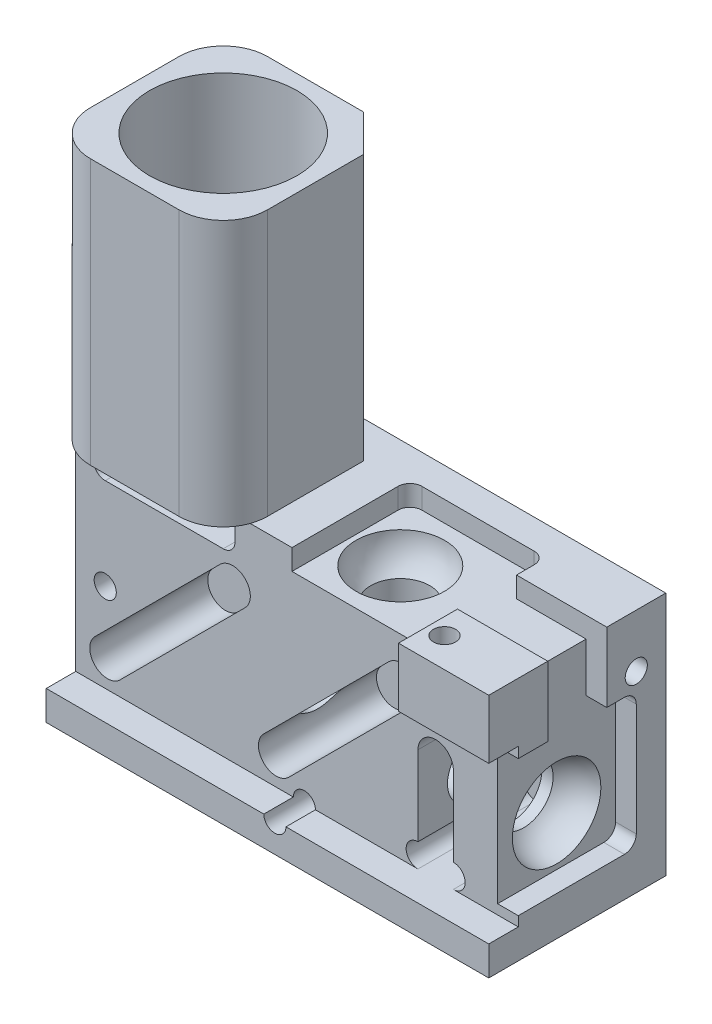
SolidWorks part; units mm, degrees
ref_plane "Front Plane" through (0, 0, 0) normal (0, 0, 1) x (1, 0, 0)
ref_plane "Top Plane" through (0, 0, 0) normal (0, 1, 0) x (1, 0, 0)
ref_plane "Right Plane" through (0, 0, 0) normal (1, 0, 0) x (0, 0, -1)
sketch "Sketch1" plane through (0, 0, 0) normal (0, 1, 0) x (1, 0, 0)
  line L1 (7.5, 3) -> (-7.5, 3)
  line L2 (7.5, 3) -> (7.5, -3)
  line L3 (7.5, -3) -> (-7.5, -3)
  line L4 (-7.5, 3) -> (-7.5, -3)
  line L5 (7.5, 3) -> (-7.5, -3) construction
  line L6 (7.5, -3) -> (-7.5, 3) construction
  point P0 (0, 0)
  dimension "D1" = 6
  dimension "D2" = 15
extrude "Main Body Ext" add sketch "Sketch1" along normal blind 8.3
sketch "Sketch8" plane through (0, 8.3, 0) normal (0, 1, 0) x (1, 0, 0)
  line L0 (-2.75, 3) -> (-1.5, 1.75)
  line L1 (-2.75, 3) -> (-7.5, 3)
  line L2 (-1.5, 1.75) -> (-1.5, -3)
  line L3 (-1.5, -3) -> (-7.5, -3)
  line L4 (-7.5, 3) -> (-7.5, -3)
  line L5 (-2.125, 2.375) -> (-7.5, -3) construction
  line L6 (-1.5, -3) -> (-7.5, 3) construction
  line L7 (-7.5, 3) -> (-7.5, -3) construction
  line L8 (0, 0) -> (-4.5, 0) construction
  point P0 (-4.5, 0)
  dimension "D1" = 6
  dimension "D2" = 6
  dimension "D3" = 1.25
  dimension "D4" = 3
extrude "Emission Path Ext" add sketch "Sketch8" along normal blind 9
sketch "Sketch3" plane through (0, 0, 0) normal (0, -1, 0) x (1, 0, 0)
  line L0 (-7.5, -3) -> (-7.5, 3) construction
  line L1 (0, 0) -> (-4.5, 0) construction
  circle A0 centre (-4.5, 0) radius 1.25
  dimension "D1" = 3
  dimension "D2" = 2.5
extrude "Emission and Grin Cut" cut sketch "Sketch3" against normal through all
sketch "Sketch4" plane through (7.5, 0, 0) normal (1, 0, 0) x (0, 0, -1)
  line L1 (-3, 0) -> (3, 0) construction
  circle A0 centre (0, 3) radius 1
  dimension "D1" = 2
  dimension "D2" = 3
extrude "Drum Lens Cut" cut sketch "Sketch4" against normal offset from surface (13 mm away) 2 up to face at (-7.5, 8.65, 0)
sketch "Sketch41" plane through (0, 8.3, 0) normal (0, 1, 0) x (1, 0, 0)
  line L1 (7.5, 3) -> (-2.75, 3) construction
  line L2 (-1.5, -3) -> (-1.5, 1.75) construction
  circle A0 centre (1.5, 0) radius 1
  dimension "D1" = 2
  dimension "D2" = 3
  dimension "D3" = 3
extrude "Addtl Light Source" cut sketch "Sketch41" against normal blind 5
sketch "Sketch5" plane through (0, 0, 3) normal (0, 0, 1) x (1, 0, 0)
  line L0 (-7.5, 0) -> (7.5, 0) construction
  line L1 (7.5, 8.3) -> (-7.5, 8.3)
  line L2 (7.5, 8.3) -> (7.5, 1)
  line L3 (7.5, 1) -> (-7.5, 1)
  line L4 (-7.5, 8.3) -> (-7.5, 1)
  line L5 (7.5, 8.3) -> (-7.5, 1) construction
  line L6 (7.5, 1) -> (-7.5, 8.3) construction
  line L7 (-1.5, 8.3) -> (7.5, 8.3) construction
  line L9 (7.5, 8.3) -> (7.5, 0) construction
  line L10 (-7.5, 17.3) -> (-7.5, 0) construction
  point P0 (0, 4.65)
  dimension "D1" = 1
extrude "FilterCover Cut1" cut sketch "Sketch5" against normal blind 1
sketch "Top-LED-Screw" plane through (0, 0, 2) normal (0, 0, 1) x (1, 0, 0)
  line L1 (7.5, 8.3) -> (4.44, 8.3)
  line L2 (7.5, 8.3) -> (7.5, 6.3)
  line L3 (7.5, 6.3) -> (4.44, 6.3)
  line L4 (4.44, 8.3) -> (4.44, 6.3)
  dimension "D1" = 2
  dimension "D2" = 3.06
extrude "Boss-Extrude1" add sketch "Top-LED-Screw" along normal blind 1
sketch "Sketch6" plane through (0, 0, 2) normal (0, 0, 1) x (1, 0, 0)
  line L0 (5.3, 4.5) -> (5.3, 1.8)
  line L1 (4.1, 4.5) -> (5.3, 4.5) construction
  line L2 (5.3, 1) -> (4.1, 1)
  line L3 (-7.5, 1) -> (7.5, 1) construction
  line L4 (-7.5, 8.3) -> (-7.5, 1) construction
  line L5 (-6.9, 7.9) -> (-6.9, 7.5)
  line L6 (4.1, 4.5) -> (4.1, 1.8)
  line L7 (-1.5, 8.3) -> (-7.5, 8.3) construction
  line L8 (-2.1, 7.9) -> (-2.1, 7.5)
  line L9 (-6, 1.5) -> (-6, 1) construction
  line L10 (-2.5, 8.3) -> (-6.5, 8.3)
  line L11 (-4.5, 3) -> (-4.5, 1) construction
  line L12 (-4.5, 3) -> (0.4851, 3) construction
  line L13 (-2.5, 7.1) -> (-6.5, 7.1)
  line L14 (-0.282, 1.5) -> (-0.282, 1) construction
  line L15 (-2.5, 8.3) -> (-6.5, 7.1) construction
  line L16 (-2.5, 7.1) -> (-6.5, 8.3) construction
  line L17 (4.1, 1.8) -> (5.3, 1.8) construction
  line L18 (-2.6059, 6.5912) -> (-6.8485, 2.3485)
  line L19 (7.5, 1) -> (7.5, 6.3) construction
  line L20 (-1.7574, 5.7426) -> (-6, 1.5)
  line L21 (-2.6059, 6.5912) -> (-6, 1.5) construction
  line L22 (-6.8485, 2.3485) -> (-1.7574, 5.7426) construction
  line L23 (1.826, 3.6081) -> (1.826, 1.6081) construction
  line L24 (1.826, 3.6081) -> (3.2165, 3.6081) construction
  line L25 (3.1121, 6.5912) -> (-1.1305, 2.3485)
  line L26 (3.9606, 5.7426) -> (-0.282, 1.5)
  line L27 (3.1121, 6.5912) -> (-0.282, 1.5) construction
  line L28 (-1.1305, 2.3485) -> (3.9606, 5.7426) construction
  line L33 (-2.5, 8.3) -> (1.102, 8.3) construction
  line L34 (1.102, 8.3) -> (1.102, 7.1) construction
  line L35 (1.102, 7.1) -> (-2.5, 7.1) construction
  line L36 (-6.5, 7.1) -> (-4.098, 7.1) construction
  line L37 (-4.098, 7.1) -> (-4.098, 8.3) construction
  line L38 (-4.098, 8.3) -> (-6.5, 8.3) construction
  line L39 (-6.5, 8.3) -> (-2.7284, 6.992) construction
  arc A0 (-2.5, 8.3) -> (-2.1, 7.9) centre (-2.5, 7.9) cw
  arc A1 (4.1, 4.5) -> (5.3, 4.5) centre (4.7, 4.5) cw
  arc A2 (-6.5, 8.3) -> (-6.9, 7.9) centre (-6.5, 7.9) ccw
  arc A3 (-2.6059, 6.5912) -> (-1.7574, 5.7426) centre (-2.1816, 6.1669) cw
  arc A4 (4.1, 1) -> (4.1, 1.8) centre (4.1, 1.4) cw
  arc A5 (-6.8485, 2.3485) -> (-6, 1.5) centre (-6.4243, 1.9243) ccw
  arc A6 (5.3, 1) -> (5.3, 1.8) centre (5.3, 1.4) ccw
  arc A7 (-6.5, 7.1) -> (-6.9, 7.5) centre (-6.5, 7.5) cw
  arc A8 (-2.5, 7.1) -> (-2.1, 7.5) centre (-2.5, 7.5) ccw
  arc A9 (3.1121, 6.5912) -> (3.9606, 5.7426) centre (3.5364, 6.1669) cw
  arc A10 (-1.1305, 2.3485) -> (-0.282, 1.5) centre (-0.7063, 1.9243) ccw
  point P5 (-4.5, 7.7)
  point P10 (-4.3029, 4.0456)
  point P21 (1.415, 4.0456)
  dimension "D10" = 0.5
  dimension "D5" = 2.2
  dimension "D8" = 0.4
  dimension "D11" = 0.4
  dimension "D12" = 0.4
  dimension "D1" = 1.2
  dimension "D2" = 45
  dimension "D3" = 3.5
  dimension "D4" = 1.2
  dimension "D6" = 2
  dimension "D7" = 4
  dimension "D9" = 3
  dimension "D13" = 1.2
  dimension "D14" = 3
  dimension "D15" = 6
  dimension "D16" = 45
  dimension "D17" = 0.5
  dimension "D18" = 1.2
  dimension "D19" = 2
  dimension "D20" = 6
extrude "FilterSet Cut2" cut sketch "Sketch6" against normal offset from surface (4 mm away) 1 up to face at (-0.0625, 9.2833, -3)
sketch "Sketch10" plane through (0, 17.3, 0) normal (0, 1, 0) x (1, 0, 0)
  line L0 (-4.5, 0) -> (-4.5, -3) construction
  line L1 (-7.5, -3) -> (-1.5, -3) construction
  line L3 (-4.5, 0) -> (-7.5, 0) construction
  line L4 (-7.5, 3) -> (-7.5, -3) construction
  circle A0 centre (-4.5, 0) radius 2.5
  dimension "D1" = 5
extrude "Emission Lens Cut" cut sketch "Sketch10" against normal offset from surface (8.5 mm away) 0.5
sketch "Sketch12" plane through (7.5, 0, 0) normal (1, 0, 0) x (0, 0, -1)
  line L0 (0, 3.635) -> (0, 0) construction
  line L1 (1.6, 5.94) -> (-1.6, 5.94)
  line L2 (1.6, 5.94) -> (1.6, 1.33) construction
  line L3 (-2, 1.33) -> (1.6, 1.33)
  line L4 (-1.6, 5.94) -> (-1.6, 1.33) construction
  line L5 (1.6, 5.94) -> (-1.6, 1.33) construction
  line L6 (1.6, 1.33) -> (-1.6, 5.94) construction
  line L7 (-3, 0) -> (3, 0) construction
  line L9 (-1.6, 5.94) -> (-2, 5.94)
  line L10 (-2, 1) -> (-2, 6.3) construction
  line L11 (-2, 5.94) -> (-2, 1.33)
  line L12 (2, 5.54) -> (2, 1.73)
  arc A1 (1.6, 5.94) -> (2, 5.54) centre (1.6, 5.54) cw
  arc A2 (1.6, 1.33) -> (2, 1.73) centre (1.6, 1.73) ccw
  circle A3 centre (0, 3) radius 1 construction
  point P0 (0, 3.635)
  dimension "D2" = 4.61
  dimension "D3" = 1.67
  dimension "D1" = 3.2
  dimension "D4" = 0.4
sketch "Sketch15" plane through (0, 0, 0) normal (0, -1, 0) x (1, 0, 0)
  line L0 (-6.25, 1.875) -> (-6.25, -1.875) construction
  line L2 (-1.5, 0) -> (-4.5, 0) construction
  line L3 (-4.5, 0) -> (-6.25, 0) construction
  circle A0 centre (-6.25, -1.875) radius 0.795
  circle A1 centre (-6.25, 1.875) radius 0.795
  circle A2 centre (-1.5, 0) radius 0.795
  dimension "D4" = 1.59
  dimension "D1" = 3.75
  dimension "D2" = 3
  dimension "D3" = 1.75
extrude "Magnets Cut" cut sketch "Sketch15" against normal blind 0.9
sketch "Sketch18" plane through (0, 0, 2) normal (0, 0, 1) x (1, 0, 0)
  line L0 (-7.5, 8.3) -> (-7.5, 1) construction
  line L1 (7.5, 1) -> (7.5, 6.3) construction
  line L2 (4.44, 8.3) -> (-1.5, 8.3) construction
  line L3 (-7.5, 0) -> (7.5, 0) construction
  line L7 (-7.5, 1) -> (4.1, 1) construction
  line L9 (-7.5, 1) -> (-7.5, 0) construction
  circle A0 centre (-6.5, 4) radius 0.375
  circle A1 centre (6, 5.8) radius 0.375
  circle A2 centre (0.25, 1) radius 0.375
  dimension "D1" = 0.75
  dimension "D2" = 1
  dimension "D3" = 2.5
  dimension "D4" = 1.5
  dimension "D5" = 3
  dimension "D6" = 1
  dimension "D7" = 7.75
extrude "Screw Holes Cut" cut sketch "Sketch18" against normal blind 2.5 and the other way through all
fillet "External Fillet 1" radius 1.5 2 edges at (-7.5, 8.65, -3)
sketch "Sketch28" plane through (0, 7.1, 0) normal (0, 1, 0) x (1, 0, 0)
  circle A0 centre (-4.5, 0) radius 1.5
  dimension "D1" = 3
extrude "Vertical-Path-Cut" cut sketch "Sketch28" against normal blind 4 and the other way through all
extrude "Cut-Extrude Original Light" cut sketch "Sketch12" against normal blind 0.7
sketch "Sketch44" plane through (0, 8.3, 0) normal (0, 1, 0) x (1, 0, 0)
  line L0 (-0.17, -2) -> (4.44, -2)
  line L1 (-0.17, -2) -> (-0.17, 1.6)
  line L2 (4.44, -2) -> (4.44, 1.6)
  line L3 (0.23, 2) -> (4.04, 2)
  line L6 (4.44, -2) -> (-1.5858, -2) construction
  circle A0 centre (1.5, 0) radius 1 construction
  arc A1 (4.44, 1.6) -> (4.04, 2) centre (4.04, 1.6) ccw
  arc A2 (-0.17, 1.6) -> (0.23, 2) centre (0.23, 1.6) cw
  point P10 (4.44, 2)
  point P13 (-0.17, 2)
  dimension "D3" = 1.67
  dimension "D4" = 0.4
  dimension "D5" = 0.4
  dimension "D1" = 4
  dimension "D2" = 4.61
extrude "Cut-Extrude Addtl Light" cut sketch "Sketch44" against normal blind 0.7
sketch "Sketch29" plane through (7.5, 0, 0) normal (1, 0, 0) x (0, 0, -1)
  line L0 (3, 8.3) -> (3, 0) construction
  line L1 (-3, 8.3) -> (3, 8.3) construction
  circle A0 centre (2, 6.5) radius 0.375
  circle A1 centre (0, 3) radius 1 construction
  dimension "D1" = 0.75
  dimension "D2" = 1
  dimension "D3" = 1.8
  dimension "D5" = 3.5
  dimension "D6" = 2
extrude "Side-LED-Screw" cut sketch "Sketch29" against normal blind 2.5
sketch "Sketch31" plane through (6.8, 0, 0) normal (1, 0, 0) x (0, 0, -1)
  circle A0 centre (0, 3) radius 1.6
  dimension "D1" = 3.2
sketch "Sketch32" plane through (7.5, 0, 0) normal (1, 0, 0) x (0, 0, -1)
  line L0 (-3, 8.3) -> (3, 8.3) construction
  line L1 (-1, 8.3) -> (1, 8.3)
  line L2 (-1, 8.3) -> (-1, 5.94)
  line L3 (-1, 5.94) -> (1, 5.94)
  line L4 (1, 8.3) -> (1, 5.94)
  line L5 (1.6, 5.94) -> (-2, 5.94) construction
  line L6 (-2, 5.94) -> (-2, 6.3) construction
  line L8 (3, 8.3) -> (3, 0) construction
  dimension "D1" = 1
  dimension "D2" = 2
extrude "Side-Wire-Slot-Cut" cut sketch "Sketch32" against normal up to surface (0.7 mm away) up to face at (6.8, 3.635, -0.5609)
sketch "Sketch45" plane through (0, 8.3, 0) normal (0, 1, 0) x (1, 0, 0)
  line L1 (4.44, -1) -> (6.8, -1)
  line L2 (4.44, -1) -> (4.44, 1)
  line L3 (4.44, 1) -> (6.8, 1)
  line L4 (6.8, -1) -> (6.8, 1)
  line L5 (4.44, -1) -> (6.8, 1) construction
  line L6 (4.44, 1) -> (6.8, -1) construction
  line L7 (6.8, 1) -> (6.8, -1) construction
  line L8 (4.44, -3) -> (4.44, 1.6) construction
  line L12 (6.8, -1) -> (7.5, -1) construction
  line L13 (6.8, 1) -> (7.5, 1) construction
extrude "Top-LED-slot" cut sketch "Sketch45" against normal blind 0.7
sketch "Sketch33" plane through (0, 0, 0) normal (0, 0, 1) x (1, 0, 0)
  line L0 (6.8, 3) -> (5.3, 3)
  line L1 (6.8, 1.4) -> (6.8, 4.6) construction
  line L2 (6.8, 3) -> (6.8, 4.5)
  arc A0 (5.3, 3) -> (6.8, 4.5) centre (6.8, 3) cw
  dimension "D2" = 1.5
revolve "Side-BallLens_Cut" cut sketch "Sketch33" angle 360 about L0
sketch "Sketch46" plane through (0, 7.6, 0) normal (0, 1, 0) x (1, 0, 0)
  circle A0 centre (1.5, 0) radius 1.5 construction
ref_plane "Plane1" through (1.5, 0, 0) normal (1, 0, 0) x (0, 0, -1)
sketch "Sketch47" plane through (1.5, 0, 0) normal (1, 0, 0) x (0, 0, -1)
  line L4 (-1.5, 7.6) -> (0, 7.6)
  line L5 (0, 7.6) -> (0, 6.1373)
  line L6 (1, 7.6) -> (-1, 7.6) construction
  arc A0 (0, 6.1373) -> (-1.5, 7.6) centre (0, 7.6378) cw
revolve "Top-BallLens_Cut" cut sketch "Sketch47" angle 360 about L5
sketch "Sketch36" plane through (0, 17.3, 0) normal (0, 1, 0) x (1, 0, 0)
  line L0 (-7.5, -1.5) -> (-7.5, -3)
  line L1 (-7.5, 1.5) -> (-7.5, -3) construction
  line L2 (-7.5, -3) -> (-6, -3)
  line L3 (-7.5, -3) -> (-3, -3) construction
  arc A0 (-7.5, -1.5) -> (-6, -3) centre (-6, -1.5) ccw
  dimension "D1" = 1.5
  dimension "D2" = 1.5
extrude "Cut-Extrude16" cut sketch "Sketch36" against normal up to surface (9 mm away) up to face at (-4.3971, 8.3, 1.2781)
sketch "Sketch37" plane through (0, 8.8, 0) normal (0, 1, 0) x (1, 0, 0)
  circle A0 centre (-4.5, 0) radius 2
  circle A1 centre (-4.5, 0) radius 1.5 construction
  dimension "D1" = 4
extrude "Cut-Extrude17" cut sketch "Sketch37" against normal up to next
sketch "Sketch51" plane through (0, 8.3, 0) normal (0, 1, 0) x (1, 0, 0)
  circle A0 centre (5, -2) radius 0.375
  circle A1 centre (1.5, 0) radius 1.5 construction
  dimension "D1" = 0.75
  dimension "D2" = 3.5
  dimension "D3" = 2
extrude "Top-LE-Screw" cut sketch "Sketch51" against normal blind 2.1
sketch "Notch" plane through (0, 0, 0) normal (0, -1, 0) x (1, 0, 0)
  line L0 (4.1286, -3) -> (3, -2.2476) construction
  line L1 (7.5, -3) -> (-6, -3) construction
  line L2 (3, -2.2476) -> (2.5865, -2.2476) construction
  line L3 (2.5865, -2.2476) -> (2.0849, -3) construction
  line L4 (3, -2.2476) -> (4.0396, -2.9406) construction
  line L5 (3, -2.2476) -> (2, -2.2476) construction
  line L6 (1.5849, -1.7476) -> (1.5849, -3)
  line L7 (5.03, -3) -> (3.1514, -1.7476)
  line L8 (3.1514, -1.7476) -> (1.5849, -1.7476)
  line L9 (1.5849, -1.7476) -> (0.75, -3)
  line L10 (5.03, -3) -> (1.5849, -3)
  line L12 (4.0396, -2.9406) -> (2.6528, -5.0208) construction
  line L13 (2.0849, -3) -> (2.0849, -2.2476) construction
  line L14 (2.0849, -2.2476) -> (2.5865, -2.2476) construction
  point P14 (0, 0)
  point P19 (1.5849, -3)
  point P20 (1.5849, -3)
  line M13 (-6, -3) -> (7.5, -3)
  dimension "D1" = 0.5
  dimension "D2" = 0.5
  dimension "D3" = 0.5
extrude "Cut-Extrude20" cut sketch "Notch" against normal blind 2 contours L7 L8 L6 M13 | L6 L9 M13 region at (2.8965, 0, -2.452) region at (1.3066, 0, -2.5825)
